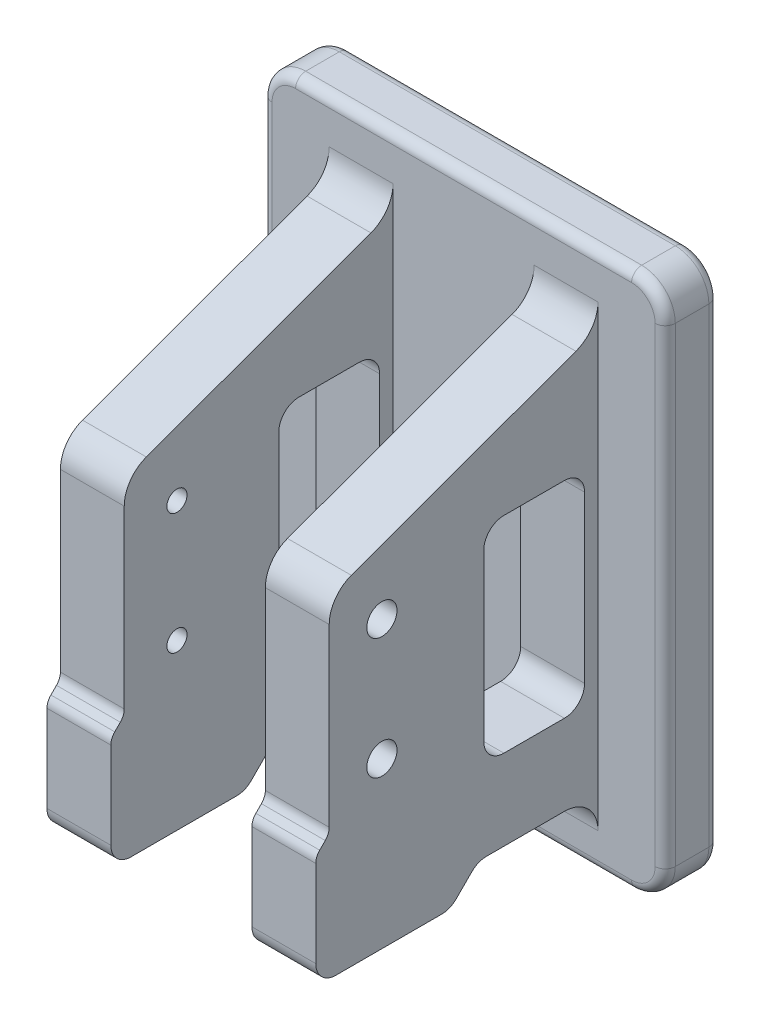
SolidWorks part; units mm, degrees
ref_plane "Front Plane" through (0, 0, 0) normal (0, 0, 1) x (1, 0, 0)
ref_plane "Top Plane" through (0, 0, 0) normal (0, 1, 0) x (1, 0, 0)
ref_plane "Right Plane" through (0, 0, 0) normal (1, 0, 0) x (0, 0, -1)
sketch "Sketch3" plane through (0, 0, 30) normal (0, 0, -1) x (-1, 0, 0)
  line L0 (95, 33.2573) -> (65, 33.2573) construction
  line L15 (80, 53.2573) -> (80, 33.2573) construction
  line L20 (55, 53.2573) -> (105, 53.2573)
  line L29 (55, -26.7427) -> (105, -26.7427)
  line L31 (110, -21.7427) -> (110, 48.2573)
  line L33 (50, -21.7427) -> (50, 48.2573)
  arc A17 (50, 48.2573) -> (55, 53.2573) centre (55, 48.2573) cw
  arc A18 (110, 48.2573) -> (105, 53.2573) centre (105, 48.2573) ccw
  arc A21 (50, -21.7427) -> (55, -26.7427) centre (55, -21.7427) ccw
  arc A22 (110, -21.7427) -> (105, -26.7427) centre (105, -21.7427) cw
  dimension "D1" = 5
extrude "Boss-Extrude1" add sketch "Sketch3" along normal blind 8
sketch "Sketch8" plane through (0, 0, 22) normal (0, 0, -1) x (-1, 0, 0)
  line L0 (50, 13.2573) -> (110, 13.2573) construction
  line L1 (50, 48.2573) -> (50, -21.7427) construction
  line L2 (110, -21.7427) -> (110, 48.2573) construction
  line L3 (80, 13.2573) -> (80, -26.7427) construction
  line L4 (55, -26.7427) -> (105, -26.7427) construction
  line L5 (78.25, 15.3786) -> (78.25, 11.136)
  line L6 (81.75, 15.3786) -> (81.75, 11.136)
  arc A0 (78.25, 11.136) -> (81.75, 11.136) centre (80, 13.2573) ccw
  arc A1 (81.75, 15.3786) -> (78.25, 15.3786) centre (80, 13.2573) ccw
extrude "Cut-Extrude3" cut sketch "Sketch8" against normal blind 3
sketch "Sketch10" plane through (0, 0, 22) normal (0, 0, -1) x (-1, 0, 0)
  line L0 (50, 13.2573) -> (110, 13.2573) construction
  line L1 (50, 48.2573) -> (50, -21.7427) construction
  line L2 (110, -21.7427) -> (110, 48.2573) construction
  line L3 (80, 13.2573) -> (80, -26.7427) construction
  line L4 (55, -26.7427) -> (105, -26.7427) construction
  line L7 (81.75, 11.136) -> (81.75, 15.3786)
  line L8 (78.25, 15.3786) -> (78.25, 11.136)
  line L9 (81.75, 11.136) -> (81.75, 15.3786)
  line L10 (78.25, 15.3786) -> (78.25, 11.136)
  circle A3 centre (80, 13.2573) radius 9.75
  arc A5 (78.25, 11.136) -> (81.75, 11.136) centre (80, 13.2573) ccw
  arc A6 (81.75, 15.3786) -> (78.25, 15.3786) centre (80, 13.2573) ccw
  arc A7 (78.25, 11.136) -> (81.75, 11.136) centre (80, 13.2573) ccw
  arc A8 (81.75, 15.3786) -> (78.25, 15.3786) centre (80, 13.2573) ccw
  dimension "D1" = 0
extrude "Boss-Extrude4" add sketch "Sketch10" along normal blind 9
fillet "Fillet2" radius 1.5 16 edges at (-80, -26.7427, 30) (-80, 53.2573, 30) (-50, 13.2573, 30) (-51.4645, 51.7928, 30) (-108.5355, 51.7928, 30) (-110, 13.2573, 30) (-80, -26.7427, 22) (-50, 13.2573, 22) (-51.4645, 51.7928, 22) (-80, 53.2573, 22) (-108.5355, 51.7928, 22) (-110, 13.2573, 22) (-108.5355, -25.2783, 22) (-51.4645, -25.2783, 22) (-108.5355, -25.2783, 30) (-51.4645, -25.2783, 30)
sketch "Sketch11" plane through (0, 0, 22) normal (0, 0, -1) x (-1, 0, 0)
  line L0 (50, 13.2573) -> (110, 13.2573) construction
  line L1 (50, -21.7427) -> (50, 48.2573) construction
  line L2 (110, 48.2573) -> (110, -21.7427) construction
  line L3 (80, 13.2573) -> (80, -26.7427) construction
  line L4 (105, -26.7427) -> (55, -26.7427) construction
  circle A0 centre (80, 13.2573) radius 11.75
extrude "Boss-Extrude5" add sketch "Sketch11" along normal blind 1
sketch "Sketch14" plane through (-70, 0, 0) normal (1, 0, 0) x (0, 0, -1)
  line L0 (-22, 1.5073) -> (-22, 25.0073) construction
  line L1 (-30, 48.2573) -> (-30, -21.7427) construction
  line L2 (-70, -1.7605) -> (-70, 28.6985)
  line L3 (-70, 28.6985) -> (-30, 43.2573)
  line L4 (-30, -16.3789) -> (-47.8764, -16.3789)
  line L6 (-30, -16.3789) -> (-30, 43.2573)
  line L7 (-47.8764, -16.3789) -> (-52, -20.5025)
  line L8 (-52, -20.5025) -> (-72, -20.5025)
  line L9 (-72, -20.5025) -> (-72, -3.7605)
  line L11 (-72, -3.7605) -> (-70, -1.7605)
  circle A6 centre (-62.1572, 3.9815) radius 1.5 construction
  circle A7 centre (-62.1572, 21.9815) radius 1.5 construction
  circle A8 centre (-62.1572, 3.9815) radius 1.5
  circle A9 centre (-62.1572, 21.9815) radius 1.5
extrude "Boss-Extrude7" add sketch "Sketch14" along normal blind 10
sketch "Sketch15" plane through (-90, 0, 0) normal (-1, 0, 0) x (0, 0, 1)
  line L4 (47.8764, -16.3789) -> (52, -20.5025)
  line L5 (70, -1.7605) -> (70, 28.6985)
  line L6 (70, 28.6985) -> (30, 43.2573)
  line L7 (30, 43.2573) -> (30, -16.3789)
  line L9 (70, -1.7605) -> (70, 28.6985)
  line L10 (70, 28.6985) -> (30, 43.2573)
  line L15 (30, 43.2573) -> (30, -16.3789)
  line L20 (47.8764, -16.3789) -> (52, -20.5025)
  line L21 (52, -20.5025) -> (72, -20.5025)
  line L22 (52, -20.5025) -> (72, -20.5025)
  line L23 (72, -20.5025) -> (72, -3.7605)
  line L24 (72, -20.5025) -> (72, -3.7605)
  line L25 (72, -3.7605) -> (70, -1.7605)
  line L26 (72, -3.7605) -> (70, -1.7605)
  line L27 (30, -16.3789) -> (47.8764, -16.3789)
  line L28 (30, -16.3789) -> (47.8764, -16.3789)
  circle A2 centre (62.1572, 3.9815) radius 1.5 construction
  circle A3 centre (62.1572, 21.9815) radius 1.5 construction
  circle A4 centre (62.1572, 3.9815) radius 1.5
  circle A5 centre (62.1572, 21.9815) radius 1.5
  dimension "D1" = 0
extrude "Boss-Extrude8" add sketch "Sketch15" along normal blind 10
fillet "Fillet3" radius 5 6 edges at (-65, 43.2573, 30) (-95, 43.2573, 30) (-95, 28.6985, 70) (-65, 28.6985, 70) (-95, -16.3789, 30) (-65, -16.3789, 30)
fillet "Fillet4" radius 3 6 edges at (-95, -20.5025, 72) (-65, -20.5025, 72) (-65, -20.5025, 52) (-95, -20.5025, 52) (-95, -16.3789, 47.8764) (-65, -16.3789, 47.8764)
sketch "Sketch16" plane through (-90, 0, 0) normal (1, 0, 0) x (0, 0, -1)
  line L8 (-72, -3.7605) -> (-72, -17.5025)
  line L9 (-69, -20.5025) -> (-53.2426, -20.5025)
  line L10 (-51.1213, -19.6238) -> (-48.7551, -17.2576)
  line L11 (-46.6337, -16.3789) -> (-35, -16.3789)
  line L12 (-30, -21.3789) -> (-30, 46.7583)
  line L13 (-33.2899, 42.0599) -> (-66.7101, 29.8959)
  line L14 (-70, 25.1974) -> (-70, -1.7605)
  line L15 (-70, -1.7605) -> (-72, -3.7605)
  line L16 (-72, -3.7605) -> (-72, -17.5025)
  line L17 (-69, -20.5025) -> (-53.2426, -20.5025)
  line L18 (-51.1213, -19.6238) -> (-48.7551, -17.2576)
  line L19 (-46.6337, -16.3789) -> (-35, -16.3789)
  line L20 (-30, -21.3789) -> (-30, 46.7583)
  line L21 (-33.2899, 42.0599) -> (-66.7101, 29.8959)
  line L22 (-70, 25.1974) -> (-70, -1.7605)
  line L23 (-70, -1.7605) -> (-72, -3.7605)
  arc A6 (-72, -17.5025) -> (-69, -20.5025) centre (-69, -17.5025) ccw
  arc A7 (-53.2426, -20.5025) -> (-51.1213, -19.6238) centre (-53.2426, -17.5025) ccw
  arc A8 (-46.6337, -16.3789) -> (-48.7551, -17.2576) centre (-46.6337, -19.3789) ccw
  arc A9 (-30, -21.3789) -> (-35, -16.3789) centre (-35, -21.3789) ccw
  arc A10 (-33.2899, 42.0599) -> (-30, 46.7583) centre (-35, 46.7583) ccw
  arc A11 (-66.7101, 29.8959) -> (-70, 25.1974) centre (-65, 25.1974) ccw
  arc A12 (-72, -17.5025) -> (-69, -20.5025) centre (-69, -17.5025) ccw
  arc A13 (-53.2426, -20.5025) -> (-51.1213, -19.6238) centre (-53.2426, -17.5025) ccw
  arc A14 (-46.6337, -16.3789) -> (-48.7551, -17.2576) centre (-46.6337, -19.3789) ccw
  arc A15 (-30, -21.3789) -> (-35, -16.3789) centre (-35, -21.3789) ccw
  arc A16 (-33.2899, 42.0599) -> (-30, 46.7583) centre (-35, 46.7583) ccw
  arc A17 (-66.7101, 29.8959) -> (-70, 25.1974) centre (-65, 25.1974) ccw
  dimension "D1" = 0
extrude "Cut-Extrude4" cut sketch "Sketch16" against normal blind 0.25
sketch "Sketch17" plane through (-70, 0, 0) normal (-1, 0, 0) x (0, 0, 1)
  line L8 (53.2426, -20.5025) -> (69, -20.5025)
  line L9 (72, -17.5025) -> (72, -3.7605)
  line L10 (72, -3.7605) -> (70, -1.7605)
  line L11 (70, -1.7605) -> (70, 25.1974)
  line L12 (66.7101, 29.8959) -> (33.2899, 42.0599)
  line L13 (30, 46.7583) -> (30, -21.3789)
  line L14 (35, -16.3789) -> (46.6337, -16.3789)
  line L15 (48.7551, -17.2576) -> (51.1213, -19.6238)
  line L16 (53.2426, -20.5025) -> (69, -20.5025)
  line L17 (72, -17.5025) -> (72, -3.7605)
  line L18 (72, -3.7605) -> (70, -1.7605)
  line L19 (70, -1.7605) -> (70, 25.1974)
  line L20 (66.7101, 29.8959) -> (33.2899, 42.0599)
  line L21 (30, 46.7583) -> (30, -21.3789)
  line L22 (35, -16.3789) -> (46.6337, -16.3789)
  line L23 (48.7551, -17.2576) -> (51.1213, -19.6238)
  arc A6 (69, -20.5025) -> (72, -17.5025) centre (69, -17.5025) ccw
  arc A7 (70, 25.1974) -> (66.7101, 29.8959) centre (65, 25.1974) ccw
  arc A8 (30, 46.7583) -> (33.2899, 42.0599) centre (35, 46.7583) ccw
  arc A9 (35, -16.3789) -> (30, -21.3789) centre (35, -21.3789) ccw
  arc A10 (48.7551, -17.2576) -> (46.6337, -16.3789) centre (46.6337, -19.3789) ccw
  arc A11 (51.1213, -19.6238) -> (53.2426, -20.5025) centre (53.2426, -17.5025) ccw
  arc A12 (69, -20.5025) -> (72, -17.5025) centre (69, -17.5025) ccw
  arc A13 (70, 25.1974) -> (66.7101, 29.8959) centre (65, 25.1974) ccw
  arc A14 (30, 46.7583) -> (33.2899, 42.0599) centre (35, 46.7583) ccw
  arc A15 (35, -16.3789) -> (30, -21.3789) centre (35, -21.3789) ccw
  arc A16 (48.7551, -17.2576) -> (46.6337, -16.3789) centre (46.6337, -19.3789) ccw
  arc A17 (51.1213, -19.6238) -> (53.2426, -20.5025) centre (53.2426, -17.5025) ccw
  dimension "D1" = 0
extrude "Cut-Extrude5" cut sketch "Sketch17" against normal blind 0.25
sketch "Sketch18" plane through (-100, 0, 0) normal (-1, 0, 0) x (0, 0, 1)
  line L0 (23.5, 53.2573) -> (28.5, 53.2573) construction
  line L1 (35, 26.2573) -> (44, 26.2573)
  line L2 (32, 23.2573) -> (32, -1.3789)
  line L3 (35, -4.3789) -> (44, -4.3789)
  line L4 (47, 23.2573) -> (47, -1.3789)
  line L5 (35, -16.3789) -> (46.6337, -16.3789) construction
  line L6 (30, 48.2573) -> (30, -21.7427) construction
  arc A0 (44, -4.3789) -> (47, -1.3789) centre (44, -1.3789) ccw
  arc A1 (32, -1.3789) -> (35, -4.3789) centre (35, -1.3789) ccw
  arc A2 (35, 26.2573) -> (32, 23.2573) centre (35, 23.2573) ccw
  arc A3 (44, 26.2573) -> (47, 23.2573) centre (44, 23.2573) cw
  point P16 (32, 26.2573)
  point P19 (47, 26.2573)
  dimension "D5" = 3
  dimension "D1" = 27
  dimension "D2" = 12
  dimension "D3" = 15
  dimension "D4" = 2
extrude "Cut-Extrude6" cut sketch "Sketch18" against normal up to surface (40 mm away) up to face at (-60, -0.7658, 53.3813)
sketch "Sketch19" plane through (-60, 0, 0) normal (1, 0, 0) x (0, 0, -1)
  circle A0 centre (-62.1572, 21.9815) radius 2.25
  circle A1 centre (-62.1572, 3.9815) radius 2.25
extrude "Cut-Extrude7" cut sketch "Sketch19" against normal blind 4
chamfer "Chamfer1" distance 1.5 angle 45 2 edges at (-100, 2.4815, 62.1572) (-100, 20.4815, 62.1572)
sketch "Sketch20" plane through (0, 0, 72) normal (0, 0, 1) x (1, 0, 0)
  line L0 (-105, 53.2573) -> (-55, 53.2573) construction
  line L1 (-90.5, 53.2573) -> (-69.5, 53.2573)
  line L2 (-90.5, 53.2573) -> (-90.5, -26.7427)
  line L3 (-90.5, -26.7427) -> (-69.5, -26.7427)
  line L4 (-69.5, 53.2573) -> (-69.5, -26.7427)
  line L5 (-55, -26.7427) -> (-105, -26.7427) construction
  line L6 (-69.75, 46.7583) -> (-69.75, 42.0599) construction
  line L7 (-90.25, 42.0599) -> (-90.25, 29.8959) construction
  dimension "D1" = 0.25
  dimension "D2" = 0.25
extrude "Cut-Extrude8" cut sketch "Sketch20" against normal up to surface (42 mm away) up to face at (-95.125, 12.6897, 30)
fillet "Fillet5" radius 2 4 edges at (-95.25, -3.7605, 72) (-95.25, -1.7605, 70) (-64.75, -3.7605, 72) (-64.75, -1.7605, 70)
